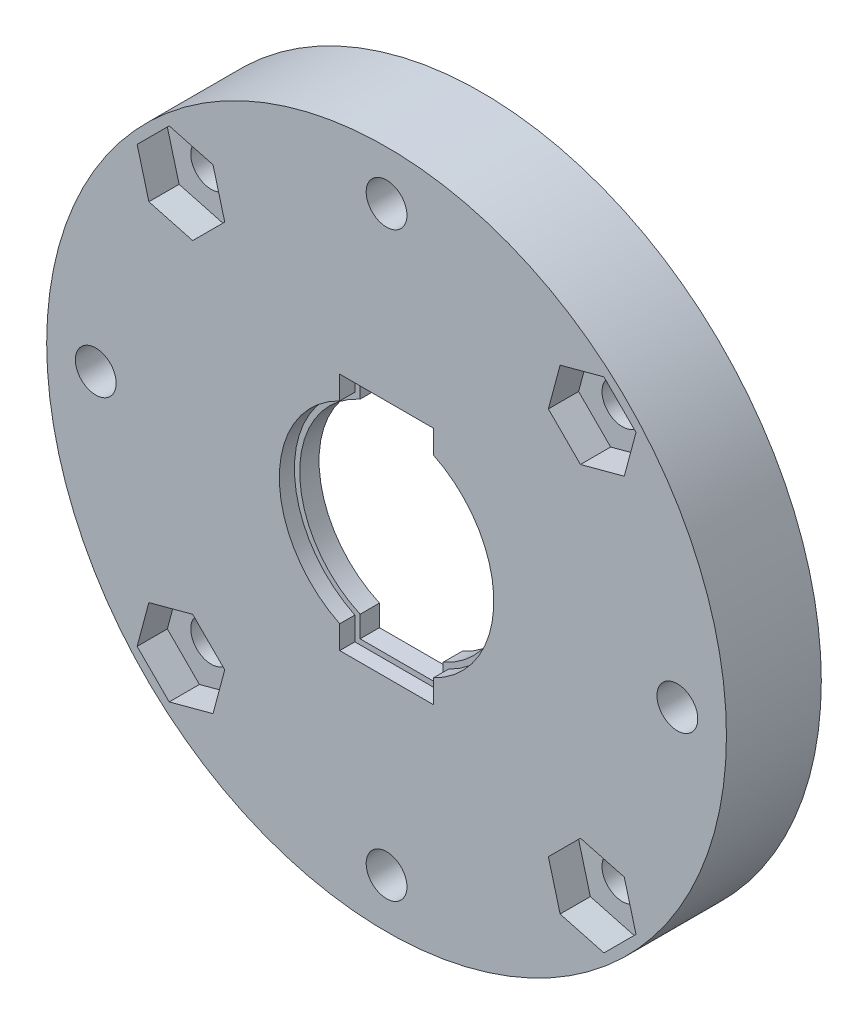
SolidWorks part; units mm, degrees
ref_plane "Front Plane" through (0, 0, 0) normal (0, 0, 1) x (1, 0, 0)
ref_plane "Top Plane" through (0, 0, 0) normal (0, 1, 0) x (1, 0, 0)
ref_plane "Right Plane" through (0, 0, 0) normal (1, 0, 0) x (0, 0, -1)
ref_axis "Z" through (0, 0, -6.594) along (0, 0, 1)
sketch "Sketch3" plane through (0, 0, 0) normal (0, 0, 1) x (1, 0, 0)
  line L0 (-3.1, -6.3875) -> (-3.1, -7.9247)
  line L1 (-3.1, -7.9247) -> (3.1, -7.9247)
  line L2 (3.1, -7.9247) -> (3.1, -6.3875)
  line L3 (3.1, 6.3875) -> (3.1, 7.9244)
  line L4 (3.1, 7.9244) -> (-3.1, 7.9244)
  line L5 (-3.1, 7.9244) -> (-3.1, 6.3875)
  line L132 (3.05, 6.3548) -> (3.05, 6.3561) construction
  line L133 (-3.05, 6.3561) -> (-3.05, 6.3548) construction
  line L134 (3.05, -6.3561) -> (3.05, -6.355) construction
  line L135 (-3.05, -6.355) -> (-3.05, -6.3561) construction
  line L198 (3.05, 6.3548) -> (3.05, 7.8744)
  line L199 (3.05, 7.8744) -> (-3.05, 7.8744)
  line L200 (-3.05, 7.8744) -> (-3.05, 6.3548)
  line L201 (-3.05, 6.3548) -> (-3.4914, 6.1247)
  line L202 (-3.4914, 6.1247) -> (-3.9416, 5.8451)
  line L203 (-3.9416, 5.8451) -> (-4.3696, 5.5325)
  line L204 (-4.3696, 5.5325) -> (-4.7729, 5.1886)
  line L205 (-4.7729, 5.1886) -> (-5.1492, 4.8154)
  line L206 (-5.1492, 4.8154) -> (-5.4964, 4.4149)
  line L207 (-5.4964, 4.4149) -> (-5.8125, 3.9896)
  line L208 (-5.8125, 3.9896) -> (-6.0958, 3.5417)
  line L209 (-6.0958, 3.5417) -> (-6.3446, 3.0737)
  line L210 (-6.3446, 3.0737) -> (-6.5576, 2.5884)
  line L211 (-6.5576, 2.5884) -> (-6.7335, 2.0885)
  line L212 (-6.7335, 2.0885) -> (-6.8714, 1.5768)
  line L213 (-6.8714, 1.5768) -> (-6.9705, 1.0561)
  line L214 (-6.9705, 1.0561) -> (-7.0301, 0.5295)
  line L215 (-7.0301, 0.5295) -> (-7.05, -0.0001)
  line L216 (-7.05, -0.0001) -> (-7.0301, -0.5297)
  line L217 (-7.0301, -0.5297) -> (-6.9705, -1.0563)
  line L218 (-6.9705, -1.0563) -> (-6.8714, -1.577)
  line L219 (-6.8714, -1.577) -> (-6.7335, -2.0887)
  line L220 (-6.7335, -2.0887) -> (-6.5576, -2.5887)
  line L221 (-6.5576, -2.5887) -> (-6.3446, -3.074)
  line L222 (-6.3446, -3.074) -> (-6.0958, -3.5419)
  line L223 (-6.0958, -3.5419) -> (-5.8125, -3.9898)
  line L224 (-5.8125, -3.9898) -> (-5.4964, -4.4152)
  line L225 (-5.4964, -4.4152) -> (-5.1492, -4.8156)
  line L226 (-5.1492, -4.8156) -> (-4.7729, -5.1888)
  line L227 (-4.7729, -5.1888) -> (-4.3696, -5.5327)
  line L228 (-4.3696, -5.5327) -> (-3.9416, -5.8453)
  line L229 (-3.9416, -5.8453) -> (-3.4914, -6.1249)
  line L230 (-3.4914, -6.1249) -> (-3.05, -6.355)
  line L231 (-3.05, -6.355) -> (-3.05, -7.8747)
  line L232 (-3.05, -7.8747) -> (3.05, -7.8747)
  line L233 (3.05, -7.8747) -> (3.05, -6.355)
  line L234 (3.05, -6.355) -> (3.4914, -6.1249)
  line L235 (3.4914, -6.1249) -> (3.9417, -5.8453)
  line L236 (3.9417, -5.8453) -> (4.3696, -5.5327)
  line L237 (4.3696, -5.5327) -> (4.7729, -5.1888)
  line L238 (4.7729, -5.1888) -> (5.1492, -4.8156)
  line L239 (5.1492, -4.8156) -> (5.4964, -4.4152)
  line L240 (5.4964, -4.4152) -> (5.8125, -3.9898)
  line L241 (5.8125, -3.9898) -> (6.0958, -3.5419)
  line L242 (6.0958, -3.5419) -> (6.3447, -3.074)
  line L243 (6.3447, -3.074) -> (6.5576, -2.5887)
  line L244 (6.5576, -2.5887) -> (6.7336, -2.0887)
  line L245 (6.7336, -2.0887) -> (6.8714, -1.577)
  line L246 (6.8714, -1.577) -> (6.9705, -1.0563)
  line L247 (6.9705, -1.0563) -> (7.0301, -0.5297)
  line L248 (7.0301, -0.5297) -> (7.05, -0.0001)
  line L249 (7.05, -0.0001) -> (7.0301, 0.5295)
  line L250 (7.0301, 0.5295) -> (6.9705, 1.0561)
  line L251 (6.9705, 1.0561) -> (6.8714, 1.5768)
  line L252 (6.8714, 1.5768) -> (6.7336, 2.0885)
  line L253 (6.7336, 2.0885) -> (6.5576, 2.5884)
  line L254 (6.5576, 2.5884) -> (6.3447, 3.0737)
  line L255 (6.3447, 3.0737) -> (6.0958, 3.5417)
  line L256 (6.0958, 3.5417) -> (5.8125, 3.9896)
  line L257 (5.8125, 3.9896) -> (5.4964, 4.4149)
  line L258 (5.4964, 4.4149) -> (5.1492, 4.8154)
  line L259 (5.1492, 4.8154) -> (4.7729, 5.1886)
  line L260 (4.7729, 5.1886) -> (4.3696, 5.5325)
  line L261 (4.3696, 5.5325) -> (3.9417, 5.8451)
  line L262 (3.9417, 5.8451) -> (3.4914, 6.1247)
  line L263 (3.4914, 6.1247) -> (3.05, 6.3548)
  line L264 (3.05, 6.3561) -> (3.05, 7.8744) construction
  line L265 (3.05, 7.8744) -> (-3.05, 7.8744) construction
  line L266 (-3.05, 7.8744) -> (-3.05, 6.3561) construction
  line L297 (-3.05, -6.3561) -> (-3.05, -7.8747) construction
  line L298 (-3.05, -7.8747) -> (3.05, -7.8747) construction
  line L299 (3.05, -7.8747) -> (3.05, -6.3561) construction
  arc A1 (-3.05, 6.3561) -> (-3.05, -6.3561) centre (0, 0) ccw construction
  arc A2 (3.05, 6.3561) -> (-3.05, 6.3561) centre (0, 0) ccw construction
  arc A3 (3.05, -6.3561) -> (3.05, 6.3561) centre (0, 0) ccw construction
  arc A4 (-3.05, -6.3561) -> (3.05, -6.3561) centre (0, 0) ccw construction
  circle A5 centre (0, 0) radius 22.5
  arc A6 (-3.1, 6.3875) -> (-3.1, -6.3875) centre (0, 0) ccw
  arc A7 (3.1, -6.3875) -> (3.1, 6.3875) centre (0, 0) ccw
  dimension "D1" = 14.1
  dimension "D3" = 45
  dimension "D2" = 0.05
  dimension "D4" = 0.05
extrude "Boss-Extrude2" add sketch "Sketch3" against normal blind 1
sketch "Sketch4" plane through (0, 0, -1) normal (0, 0, -1) x (-1, 0, 0)
  line L39 (2.75, 6.1644) -> (2.75, 7.5744)
  line L40 (2.75, 7.5744) -> (-2.75, 7.5744)
  line L41 (-2.75, 7.5744) -> (-2.75, 6.1644)
  line L42 (-2.75, -6.1644) -> (-2.75, -7.5747)
  line L43 (-2.75, -7.5747) -> (2.75, -7.5747)
  line L44 (2.75, -7.5747) -> (2.75, -6.1644)
  circle A14 centre (0, 0) radius 22.5
  arc A17 (-2.75, 6.1644) -> (-2.75, -6.1644) centre (0, 0) ccw
  arc A18 (2.75, -6.1644) -> (2.75, 6.1644) centre (0, 0) ccw
  dimension "D1" = 45
extrude "Boss-Extrude3" add sketch "Sketch4" along normal blind 5.28
sketch "Sketch5" plane through (0, 0, -6.28) normal (0, 0, -1) x (-1, 0, 0)
  circle A0 centre (0, 0) radius 17.25
  dimension "D1" = 34.5
extrude "Cut-Extrude1" cut sketch "Sketch5" against normal blind 4
sketch "Sketch6" plane through (0, 0, 0) normal (0, 0, 1) x (1, 0, 0)
  line L0 (0, 0) -> (13.6118, 13.6118) construction
  line L1 (-16.3801, 0) -> (0, 0) construction
  line L3 (14.3888, 16.5117) -> (11.4889, 15.7347)
  line L4 (11.4889, 15.7347) -> (10.7119, 12.8348)
  line L5 (10.7119, 12.8348) -> (12.8348, 10.7119)
  line L6 (12.8348, 10.7119) -> (15.7347, 11.4889)
  line L7 (15.7347, 11.4889) -> (16.5117, 14.3888)
  line L8 (16.5117, 14.3888) -> (14.3888, 16.5117)
  circle A0 centre (13.6118, 13.6118) radius 2.6 construction
  dimension "D1" = 135
  dimension "D2" = 19.25
  dimension "D3" = 5.2
extrude "Cut-Extrude2" cut sketch "Sketch6" against normal blind 2
sketch "Sketch8" plane through (0, 0, 0) normal (0, 0, 1) x (1, 0, 0)
  line L0 (36.6653, 0) -> (49.0214, 0) construction
  line L1 (0, 0) -> (13.6118, 13.6118) construction
  circle A0 centre (0, 0) radius 19.25 construction
  circle A1 centre (13.6118, 13.6118) radius 1.35
  dimension "D1" = 38.5
  dimension "D3" = 2.7
  dimension "D2" = 135
extrude "Cut-Extrude4" cut sketch "Sketch8" against normal through all
pattern_circular "CirPattern1" count 4 over 360 about axis through (0, 0, -6.594) along (0, 0, 1) of "Cut-Extrude2", "Cut-Extrude4"
ref_plane "Plane4" through (0, 0, 0) normal (-0.7071, 0.7071, 0) x (0, 0, 1)
pattern_circular "CirPattern2" count 8 over 360 about axis through (0, 0, -6.594) along (0, 0, 1) of "Cut-Extrude4"
equation "\"BearingBaseDistance\"= 10"
equation "\"BearingOD\"= 32"
equation "\"BearingID\" = 25"
equation "\"BearingHeight\"= 4"
equation "\"SeatsOD\"= \"BearingOD\" + 10"
equation "\"WireHarnessHeight\"= 4"
equation "\"OuterWallWidth\"= 6"
equation "\"OverallOD\" = 45"
equation "\"OuterHousingHeight\" = \"WireHarnessHeight\" + \"BearingHeight\"*2 + \"BearingBaseDistance\""
equation "\"RetainingRingThickness\" = 1.30"
equation "\"RetaininRingGrooveDiameter\" = 23.9"
equation "\"ShaftLengthAfterFlange\" = 2*\"BearingHeight\" + \"BearingBaseDistance\" + \"RetainingRingThickness\"*2\t'give a retaining ring thickness of extra clearance"
equation "\"RetainingRingGrooveBase\" = \"ShaftLengthAfterFlange\" - \"RetainingRingThickness\"*2"
equation "\"CoverThickness\" = 1"
equation "\"CoverClearance\" = 1"
equation "\"FlangHeight\" = \"CoverThickness\" + \"CoverClearance\" + \"WireHarnessHeight\""
equation "\"PCBWidth\" = 5"
equation "\"PCBHeight\" = \"OuterHousingHeight\" "
equation "\"PCBThickness\" = 1"
equation "\"NormalDistSidewallPCBToZ\" = (\"OverallOD\"/2) - 1.6\t'radial distance from the z axis to pcb origin on the top/connector side"
equation "\"PCBSidewallCutoutClearance\" = 0.1"
equation "\"OutputHubBoltCircleRadius\" = 8"
equation "\"OutputHubOD\" = 27"
equation "\"StatorWireRadius\" = \"NormalDistSidewallPCBToZ\" - 5.7"
equation "\"MountingHoleRadius\" = (\"OverallOD\"+\"BearingOD\")/4"
equation "\"D3@Sketch3\"=\"OverallOD\""
equation "\"D1@Sketch4\"=\"OverallOD\""
equation "\"D1@Sketch8\"=\"MountingHoleRadius\"*2"
equation "\"D2@Sketch6\"=(\"OverallOD\"+\"BearingOD\")/4"
